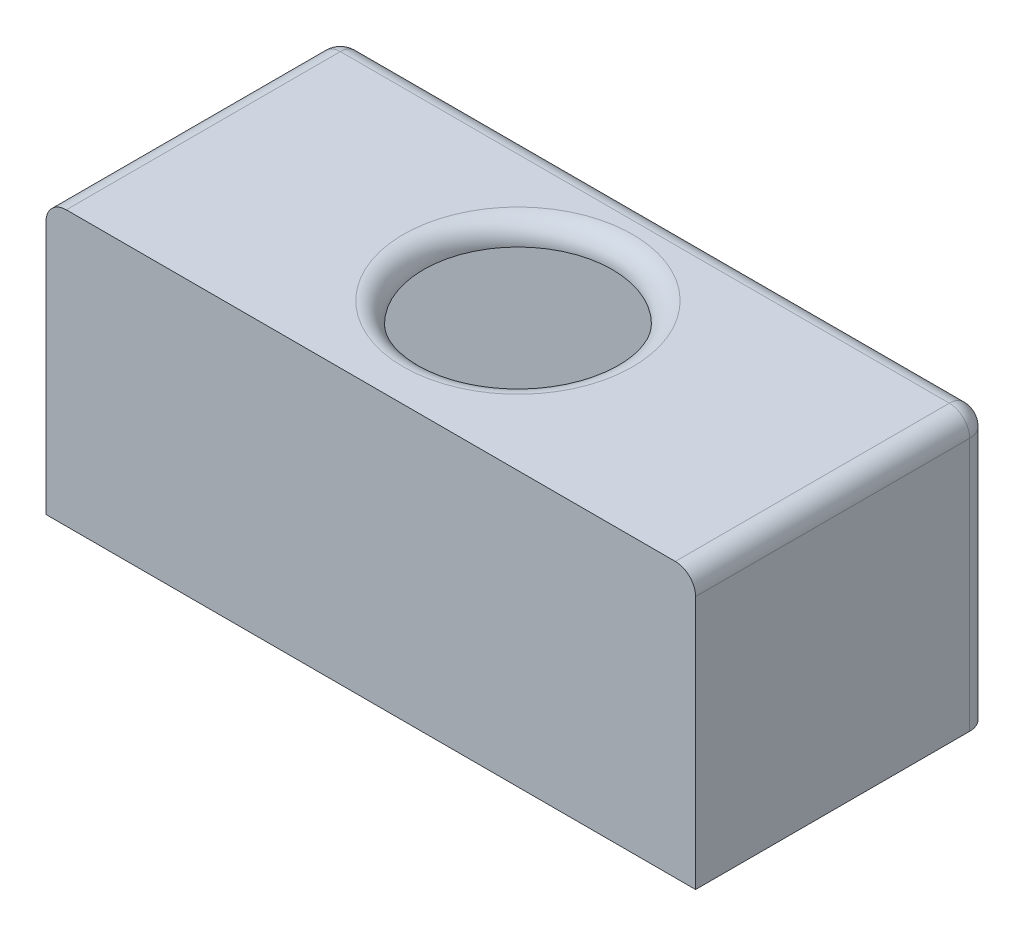
SolidWorks part; units mm, degrees
ref_plane "Front Plane" through (0, 0, 0) normal (0, 0, 1) x (1, 0, 0)
ref_plane "Top Plane" through (0, 0, 0) normal (0, 1, 0) x (1, 0, 0)
ref_plane "Right Plane" through (0, 0, 0) normal (1, 0, 0) x (0, 0, -1)
sketch "Sketch1" plane through (0, 0, 0) normal (0, 1, 0) x (1, 0, 0)
  line L1 (-28.9693, 17.2654) -> (47.2307, 17.2654)
  line L2 (-28.9693, 17.2654) -> (-28.9693, -14.4846)
  line L3 (-28.9693, -14.4846) -> (47.2307, -14.4846)
  line L4 (47.2307, 17.2654) -> (47.2307, -14.4846)
  dimension "D1" = 76.2
  dimension "D2" = 31.75
extrude "Boss-Extrude1" add sketch "Sketch1" along normal blind 31.75
shell "Shell4" thickness 2.54 removed face at (9.1307, 0, -1.3904) outward yes
sketch "Sketch2" plane through (0, 0, 0) normal (0, 1, 0) x (1, 0, 0)
  line L0 (9.0828, 21.694) -> (9.1307, -17.0246) construction
  line L1 (-31.5093, -17.0246) -> (49.7707, -17.0246) construction
  line L2 (-31.5093, 1.3904) -> (49.7707, 1.3904) construction
  line L3 (-31.5093, 19.8054) -> (-31.5093, -17.0246) construction
  line L4 (49.7707, -17.0246) -> (49.7707, 19.8054) construction
  circle A0 centre (9.1307, 1.3904) radius 11.811
  dimension "D1" = 23.622
extrude "Cut-Extrude5" cut sketch "Sketch2" against normal mid plane 25.4 from surface starting at face at (9.1307, 34.29, -1.3904)
fillet "Fillet3" radius 2.54 6 edges at (49.7707, 34.29, -1.3904) (-31.5093, 34.29, -1.3904) (9.1307, 34.29, -19.8054) (49.7707, 17.145, -19.8054) (-31.5093, 17.145, -19.8054) (9.1307, 34.29, 10.4206)
